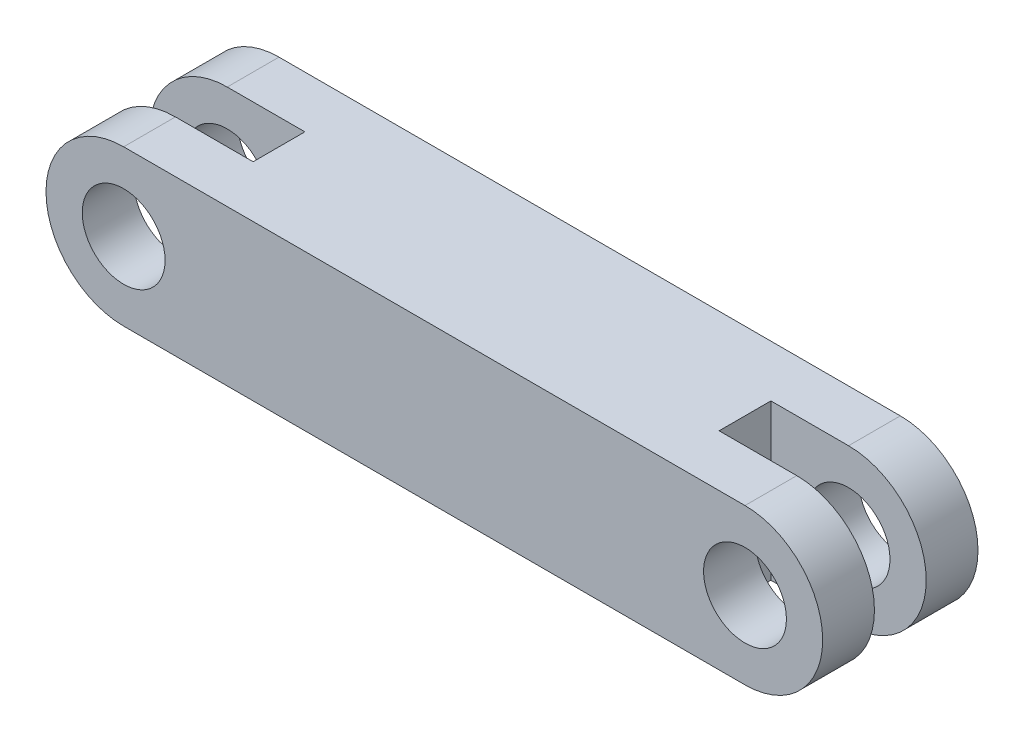
SolidWorks part; units mm, degrees
ref_plane "Front" through (0, 0, 0) normal (0, 0, 1) x (1, 0, 0)
ref_plane "Top" through (0, 0, 0) normal (0, 1, 0) x (1, 0, 0)
ref_plane "Right" through (0, 0, 0) normal (1, 0, 0) x (0, 0, -1)
sketch "Sketch1" plane through (0, 0, 0) normal (0, 0, 1) x (1, 0, 0)
  line L0 (-47.2174, 0.4239) -> (12.7826, 0.4239) construction
  line L1 (-47.2174, 7.9239) -> (12.7826, 7.9239)
  line L2 (-47.2174, -7.0761) -> (12.7826, -7.0761)
  arc A0 (-47.2174, 7.9239) -> (-47.2174, -7.0761) centre (-47.2174, 0.4239) ccw
  arc A1 (12.7826, -7.0761) -> (12.7826, 7.9239) centre (12.7826, 0.4239) ccw
  circle A2 centre (-47.2174, 0.4239) radius 4
  circle A3 centre (12.7826, 0.4239) radius 4
  point P2 (-17.2174, 0.4239)
  dimension "D1" = 7.5
  dimension "D2" = 60
extrude "Boss-Extrude1" add sketch "Sketch1" along normal blind 5
sketch "Sketch2" plane through (0, 0, 5) normal (0, 0, 1) x (1, 0, 0)
  line L2 (-39.7174, -7.0761) -> (-39.7174, 7.9239)
  line L3 (5.2826, -7.0761) -> (5.2826, 7.9239)
  line L4 (12.7826, 7.9239) -> (-47.2174, 7.9239) construction
  line L5 (5.2826, 7.9239) -> (-39.7174, 7.9239)
  line L6 (-39.7174, -7.0761) -> (5.2826, -7.0761)
  point P13 (-39.7174, 0.4239)
  point P16 (5.2826, 0.4239)
extrude "Boss-Extrude2" add sketch "Sketch2" along normal blind 5
sketch "Sketch5" plane through (0, 0, 10) normal (0, 0, 1) x (1, 0, 0)
  line L0 (-47.2174, 0.4239) -> (12.7826, 0.4239) construction
  line L1 (-47.2174, 7.9239) -> (12.7826, 7.9239)
  line L2 (-47.2174, -7.0761) -> (12.7826, -7.0761)
  arc A0 (-47.2174, 7.9239) -> (-47.2174, -7.0761) centre (-47.2174, 0.4239) ccw
  arc A1 (12.7826, -7.0761) -> (12.7826, 7.9239) centre (12.7826, 0.4239) ccw
  circle A2 centre (-47.2174, 0.4239) radius 4
  circle A3 centre (12.7826, 0.4239) radius 4
  point P4 (-17.2174, 0.4239)
  dimension "D1" = 7.5
extrude "Boss-Extrude3" add sketch "Sketch5" along normal blind 5
